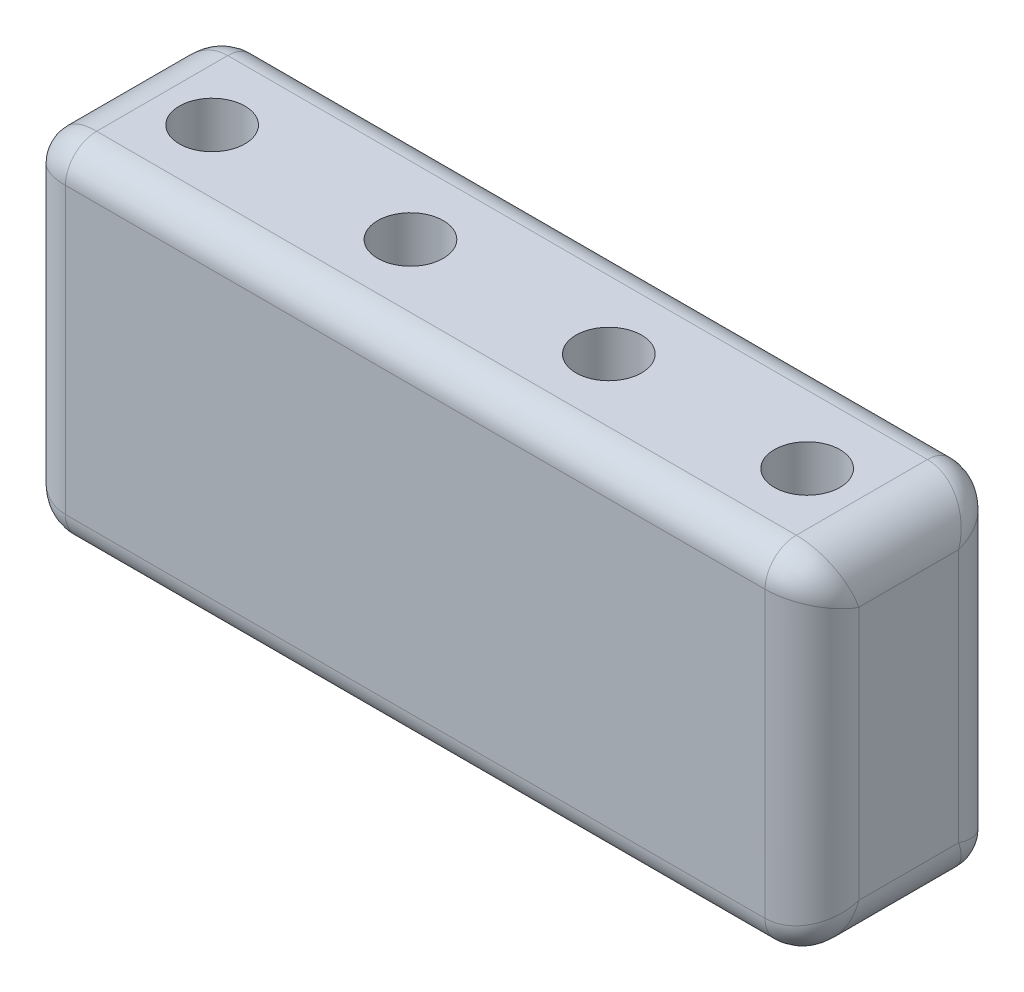
SolidWorks part; units mm, degrees
ref_plane "Front Plane" through (0, 0, 0) normal (0, 0, 1) x (1, 0, 0)
ref_plane "Top Plane" through (0, 0, 0) normal (0, 1, 0) x (1, 0, 0)
ref_plane "Right Plane" through (0, 0, 0) normal (1, 0, 0) x (0, 0, -1)
sketch "Sketch1" plane through (0, 0, 0) normal (0, 0, 1) x (1, 0, 0)
  line L1 (0, 0) -> (-50.8, 0)
  line L2 (0, 0) -> (0, -22.2504)
  line L3 (0, -22.2504) -> (-50.8, -22.2504)
  line L4 (-50.8, 0) -> (-50.8, -22.2504)
  dimension "D1" = 22.2504
  dimension "D2" = 50.8
extrude "Boss-Extrude1" add sketch "Sketch1" along normal blind 12.3952
sketch "Sketch2" plane through (0, 0, 0) normal (0, 1, 0) x (1, 0, 0)
  line L0 (0, 0) -> (-50.8, 0) construction
  line L1 (-50.8, -12.3952) -> (-50.8, 0) construction
  circle A0 centre (-44.45, -6.35) radius 2.1
  circle A1 centre (-6.35, -6.35) radius 2.1
  circle A2 centre (-31.75, -6.35) radius 2.1
  circle A3 centre (-19.05, -6.35) radius 2.1
  point P8 (0, 0)
  dimension "D1" = 4.2
  dimension "D2" = 4.2
  dimension "D3" = 4.2
  dimension "D4" = 4.2
  dimension "D5" = 6.35
  dimension "D6" = 12.7
  dimension "D7" = 12.7
  dimension "D8" = 12.7
  dimension "D9" = 6.35
extrude "Cut-Extrude1" cut sketch "Sketch2" against normal up to next
fillet "Fillet1" radius 2 4 edges at (-25.4, -22.2504, 0) (-25.4, -22.2504, 12.3952) (-25.4, 0, 0) (-25.4, 0, 12.3952)
fillet "Fillet2" radius 3 16 edges at (0, -21.6646, 11.8094) (0, -22.2504, 6.1976) (0, -21.6646, 0.5858) (0, -11.1252, 0) (0, -0.5858, 0.5858) (0, 0, 6.1976) (0, -0.5858, 11.8094) (-50.8, -0.5858, 11.8094) (-50.8, 0, 6.1976) (-50.8, -0.5858, 0.5858) (-50.8, -11.1252, 0) (-50.8, -21.6646, 0.5858) (-50.8, -22.2504, 6.1976) (-50.8, -21.6646, 11.8094) (0, -11.1252, 12.3952) (-50.8, -11.1252, 12.3952)
